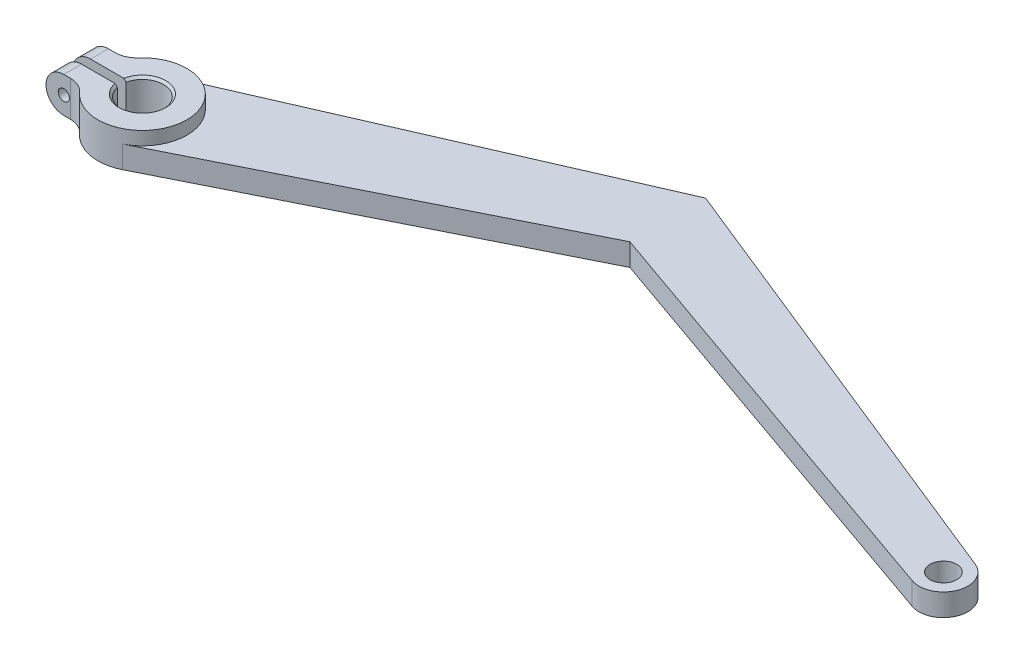
SolidWorks part; units mm, degrees
ref_plane "Front Plane" through (0, 0, 0) normal (0, 0, 1) x (1, 0, 0)
ref_plane "Top Plane" through (0, 0, 0) normal (0, 1, 0) x (1, 0, 0)
ref_plane "Right Plane" through (0, 0, 0) normal (1, 0, 0) x (0, 0, -1)
sketch "Sketch1" plane through (0, 0, 0) normal (0, 1, 0) x (1, 0, 0)
  line L0 (0, 0) -> (-42.5984, 0) construction
  line L1 (-16.6603, -5) -> (-16.6603, -1)
  line L2 (-16.6603, 5) -> (-8.6603, 5)
  line L3 (-16.6603, -5) -> (-8.6603, -5)
  line L4 (-16.6603, 1) -> (-4.6487, 1)
  line L5 (-16.6603, -1) -> (-4.6487, -1)
  line L6 (-16.6603, 1) -> (-16.6603, 5)
  arc A0 (-4.6487, -1) -> (-4.6487, 1) centre (0, 0) ccw
  arc A1 (-8.6603, -5) -> (-8.6603, 5) centre (0, 0) ccw
  point P8 (-42.5984, 0)
  dimension "D1" = 4.755
  dimension "D5" = 10
  dimension "D2" = 4
  dimension "D3" = 1
  dimension "D4" = 8
extrude "Boss-Extrude1" add sketch "Sketch1" along normal blind 8
sketch "Sketch2" plane through (0, 0, 0) normal (0, 1, 0) x (1, 0, 0)
  line L0 (0, 0) -> (180, 0) construction
  line L1 (182.0566, 5.101) -> (80.5083, 46.0416)
  line L2 (80.5083, 46.0416) -> (-3.9995, 9.1654)
  line L3 (178.1809, -5.1904) -> (80.5083, 29.0416)
  line L4 (80.5083, 29.0416) -> (4.4691, -8.9458)
  line L5 (80.5083, 46.0416) -> (80.5083, 29.0416) construction
  line L6 (0, 0) -> (80.5083, 37.5416) construction
  line L7 (80.5083, 37.5416) -> (180, 0) construction
  arc A0 (-8.6603, -5) -> (-8.6603, 5) centre (0, 0) ccw construction
  arc A1 (4.4691, -8.9458) -> (-3.9995, 9.1654) centre (0, 0) ccw
  circle A2 centre (180, 0) radius 3
  arc A3 (178.1809, -5.1904) -> (182.0566, 5.101) centre (180, 0) ccw
  dimension "D2" = 6
  dimension "D3" = 5.5
  dimension "D1" = 180
  dimension "D4" = 85
  dimension "D5" = 25
  dimension "D6" = 17
extrude "Boss-Extrude2" add sketch "Sketch2" along normal blind 5
sketch "Sketch3" plane through (0, 0, -5) normal (0, 0, -1) x (-1, 0, 0)
  line L0 (16.6603, 4) -> (8.6603, 4) construction
  line L1 (16.6603, 8) -> (16.6603, 0) construction
  line L2 (8.6603, 8) -> (8.6603, 0) construction
  line L3 (12.6603, 8) -> (12.6603, 0) construction
  line L4 (8.6603, 8) -> (16.6603, 8) construction
  line L5 (8.6603, 0) -> (16.6603, 0) construction
  point P12 (12.6603, 4)
hole_wizard "CBORE for M3 SHCS1" positions "Sketch8" profile "Sketch9" counterbore size "M3" standard "ANSI Metric"
sketch "Sketch8" plane through (0, 0, -5) normal (0, 0, -1) x (-1, 0, 0)
  point P0 (12.6603, 4)
sketch "Sketch9" plane through (-12.6603, 4, -5) normal (1, 0, 0) x (0, 1, 0)
  line L0 (0, 0) -> (0, 5.9614)
  line L1 (0, 5.9614) -> (1.6, 5)
  line L2 (1.6, 5) -> (1.6, 3)
  line L3 (1.6, 3) -> (3.25, 3)
  line L4 (3.25, 3) -> (3.25, 0)
  line L5 (3.25, 0) -> (0, 0)
  line L10 (0, 5.9614) -> (-1.6, 5) construction
  line L11 (0, -6.35) -> (0, 107.95) construction
  dimension "Hole Dia." = 3.2
  dimension "Hole Depth" = 5
  dimension "C'Bore Dia." = 6.5
  dimension "C'Bore Depth" = 3
  dimension "Drill Angle" = 118
sketch "Sketch10" plane through (0, 0, 1) normal (0, 0, -1) x (-1, 0, 0)
  point P0 (12.6603, 4)
hole_wizard "M3x0.5 Tapped Hole1" positions "Sketch12" profile "Sketch11" tap size "M3x0.5" standard "ANSI Metric" end condition through all
sketch "Sketch12" plane through (0, 0, 1) normal (0, 0, -1) x (-1, 0, 0)
  point P0 (12.6603, 4)
sketch "Sketch11" plane through (-12.6603, 4, 1) normal (1, 0, 0) x (0, 1, 0)
  line L0 (0, 0) -> (0, 9)
  line L1 (0, 9) -> (1.25, 9)
  line L2 (1.25, 9) -> (1.25, 0)
  line L5 (1.25, 0) -> (0, 0)
  line L11 (0, -6.35) -> (0, 107.95) construction
  dimension "Thru Tap Drill Dia." = 2.5
  dimension "Thru Tap Drill Depth" = 9
cosmetic thread "Hole Thread1" parameters "D2"=3
fillet "Fillet1" radius 4 4 edges at (-16.6603, 8, 3) (-16.6603, 0, 3) (-16.6603, 0, -3) (-16.6603, 8, -3)
fillet "Fillet2" radius 5 2 edges at (-8.6603, 4, 5) (-8.6603, 4, -5)
chamfer "Chamfer1" distance 0.5 angle 45 2 edges at (4.755, 0, 0) (4.755, 8, 0)
sketch "Sketch14" plane through (0, 5, 0) normal (0, 1, 0) x (1, 0, 0)
  line L0 (180, 0) -> (0, 0) construction
